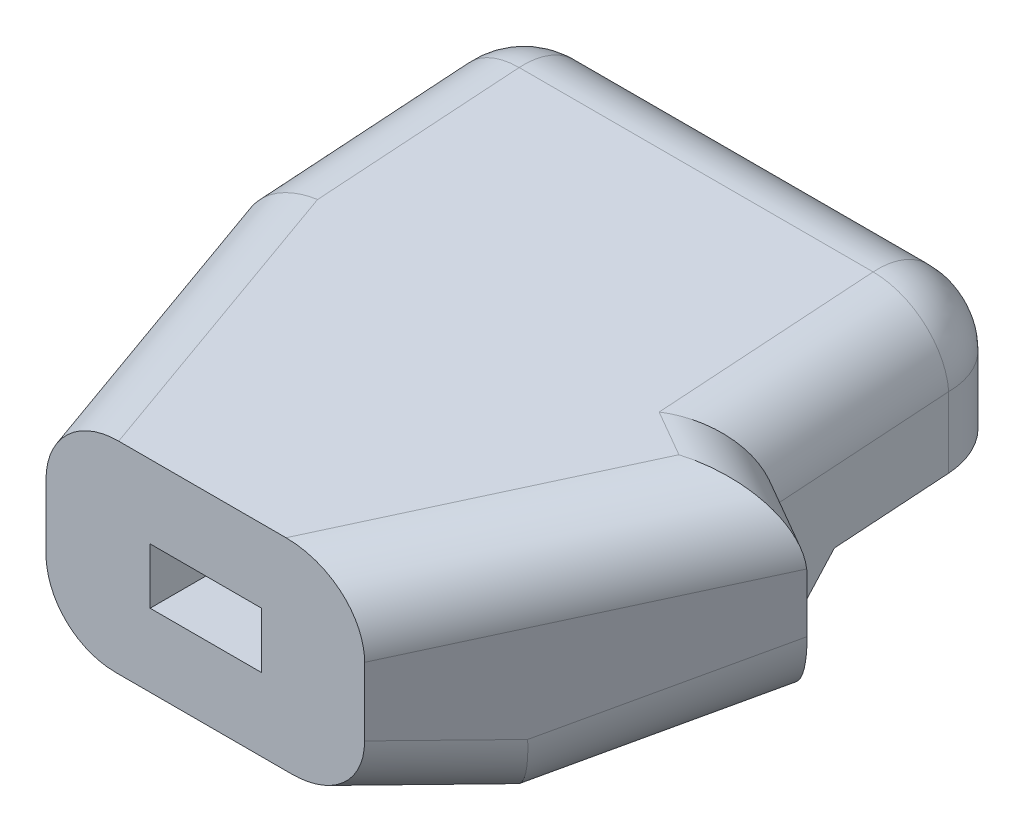
SolidWorks part; units mm, degrees
ref_plane "Front" through (0, 0, 0) normal (0, 0, 1) x (1, 0, 0)
ref_plane "Top" through (0, 0, 0) normal (0, 1, 0) x (1, 0, 0)
ref_plane "Right" through (0, 0, 0) normal (1, 0, 0) x (0, 0, -1)
sketch "Sketch1" plane through (0, 0, 0) normal (0, 1, 0) x (1, 0, 0)
  line L0 (-44.45, 101.6) -> (44.45, 101.6)
  line L2 (57.15, 50.8) -> (28.575, 0)
  line L3 (28.575, 0) -> (-28.575, 0)
  line L4 (-28.575, 0) -> (-44.45, 50.8)
  line L6 (-44.45, 50.8) -> (-44.45, 101.6)
  line L7 (0, 0) -> (0, 101.6) construction
  line L8 (57.15, 50.8) -> (44.45, 57.9437)
  line L9 (44.45, 57.9437) -> (44.45, 101.6)
  dimension "D1" = 88.9
  dimension "D2" = 57.15
  dimension "D3" = 101.6
  dimension "D4" = 50.8
  dimension "D5" = 12.7
extrude "Extrude1" add sketch "Sketch1" along normal blind 48.26
ref_axis "Axis1" through (0, 0, 22.3254) along (0, 0, -1)
sketch "Sketch3" plane through (-44.45, 0, 0) normal (-1, 0, 0) x (0, 0, 1)
  line L0 (0, 41.4453) -> (-101.6, 48.26)
  line L1 (0, 48.26) -> (0, 0) construction
  line L2 (0, 5.2406) -> (-25.4, 0)
  line L3 (-50.8, 0) -> (0, 0) construction
  line L4 (-25.4, 0) -> (-57.9437, 9.0846)
  line L6 (-57.9437, 9.0846) -> (-68.3976, 20.633)
  line L7 (-68.3976, 20.633) -> (-101.6, 22.86)
  line L9 (-57.9437, 48.26) -> (-57.9437, 0) construction
  line L10 (0, 5.2406) -> (0, 41.4453)
  line L11 (-101.6, 48.26) -> (-101.6, 22.86)
  dimension "D1" = 25.4
extrude "Cut-Extrude1" cut sketch "Sketch3" against normal mid plane 254 flip side to cut
sketch "Sketch4" plane through (24.2408, 0, -69.3114) normal (-0.4903, 0, 0.8716) x (0.8716, 0, 0.4903)
  line L2 (23.187, 45.3318) -> (37.7583, 7.0904) construction
  point P0 (30.4727, 26.2111)
sketch "Sketch5" plane through (20.8472, -1.8972, -101.6) normal (0, 0, -1) x (-1, 0, 0)
  line L0 (-23.6028, 37.4572) -> (65.2972, 37.4572) construction
  line L1 (-23.6028, 50.1572) -> (-23.6028, 24.7572) construction
  line L4 (65.2972, 50.1572) -> (65.2972, 24.7572) construction
  point P0 (-10.2057, 37.4572)
  point P1 (11.0496, 37.4572)
  point P2 (31.9024, 37.4572)
  point P3 (53.5765, 37.4572)
sketch "Sketch7" plane through (0, 0, 0) normal (0, 0, 1) x (1, 0, 0)
  line L0 (-28.575, 41.4453) -> (28.575, 5.2406) construction
  line L1 (-28.575, 5.2406) -> (28.575, 41.4453) construction
  point P0 (0, 23.3429)
fillet "Fillet1" radius 12.7 8 edges at (-44.45, 35.56, -101.6) (-44.45, 46.5563, -76.2) (42.8625, 43.149, -25.4) (0, 48.26, -101.6) (50.8, 45.0922, -54.3719) (44.45, 35.56, -101.6) (44.45, 46.7959, -79.7719) (-36.5125, 43.149, -25.4)
fillet "Fillet2" radius 12.7 4 edges at (-40.4813, 3.5452, -38.1) (-32.5438, 2.6203, -12.7) (50.0062, 3.5452, -38.1) (35.7187, 2.6203, -12.7)
sketch "Sketch8" plane through (0, 0, 0) normal (0, 0, 1) x (1, 0, 0)
  line L1 (-9.8958, 18.3064) -> (10.1042, 18.3064)
  line L2 (-9.8958, 18.3064) -> (-9.8958, 28.3064)
  line L3 (-9.8958, 28.3064) -> (10.1042, 28.3064)
  line L4 (-28.575, 28.9708) -> (-28.575, 17.4265)
  line L5 (-16.0713, 5.2406) -> (15.4472, 5.2406)
  line L6 (28.575, 16.9235) -> (28.575, 29.1344)
  line L7 (14.4818, 41.4453) -> (-15.5349, 41.4453)
  line L8 (-28.575, 28.9708) -> (-28.575, 17.4265)
  line L9 (-16.0713, 5.2406) -> (15.4472, 5.2406)
  line L10 (28.575, 16.9235) -> (28.575, 29.1344)
  line L11 (14.4818, 41.4453) -> (-15.5349, 41.4453)
  line L12 (10.1042, 18.3064) -> (10.1042, 28.3064)
  line L13 (-9.8958, 18.3064) -> (10.1042, 28.3064) construction
  line L14 (-9.8958, 28.3064) -> (10.1042, 18.3064) construction
  ellipse E4 centre (-15.2693, 18.2081) end of major axis (-3.9522, 25.68) minor radius 12.7 (-28.575, 17.4265) -> (-16.0713, 5.2406) ccw
  ellipse E5 centre (14.0037, 18.2081) end of major axis (0.1042, 23.3064) minor radius 12.7 (15.4472, 5.2406) -> (28.575, 16.9235) ccw
  ellipse E6 centre (14.0037, 28.7168) end of major axis (-0.4898, 26.9885) minor radius 12.7 (28.575, 29.1344) -> (14.4818, 41.4453) ccw
  ellipse E7 centre (-15.2693, 28.7168) end of major axis (-2.2333, 25.9187) minor radius 12.7 (-15.5349, 41.4453) -> (-28.575, 28.9708) ccw
  ellipse E8 centre (-15.2693, 18.2081) end of major axis (-3.9522, 25.68) minor radius 12.7 (-28.575, 17.4265) -> (-16.0713, 5.2406) ccw
  ellipse E9 centre (14.0037, 18.2081) end of major axis (27.9032, 13.1098) minor radius 12.7 (15.4472, 5.2406) -> (28.575, 16.9235) ccw
  ellipse E10 centre (14.0037, 28.7168) end of major axis (-0.4898, 26.9885) minor radius 12.7 (28.575, 29.1344) -> (14.4818, 41.4453) ccw
  ellipse E11 centre (-15.2693, 28.7168) end of major axis (-28.3053, 31.5148) minor radius 12.7 (-15.5349, 41.4453) -> (-28.575, 28.9708) ccw
  point P4 (0.1042, 23.3064)
  dimension "D2" = 20
  dimension "D3" = 10
  dimension "D1" = 0
extrude "Cut-Extrude2" cut sketch "Sketch8" against normal blind 12.7 contours L1 L12 L3 L2 region at (0.1042, 23.3064, 0)
